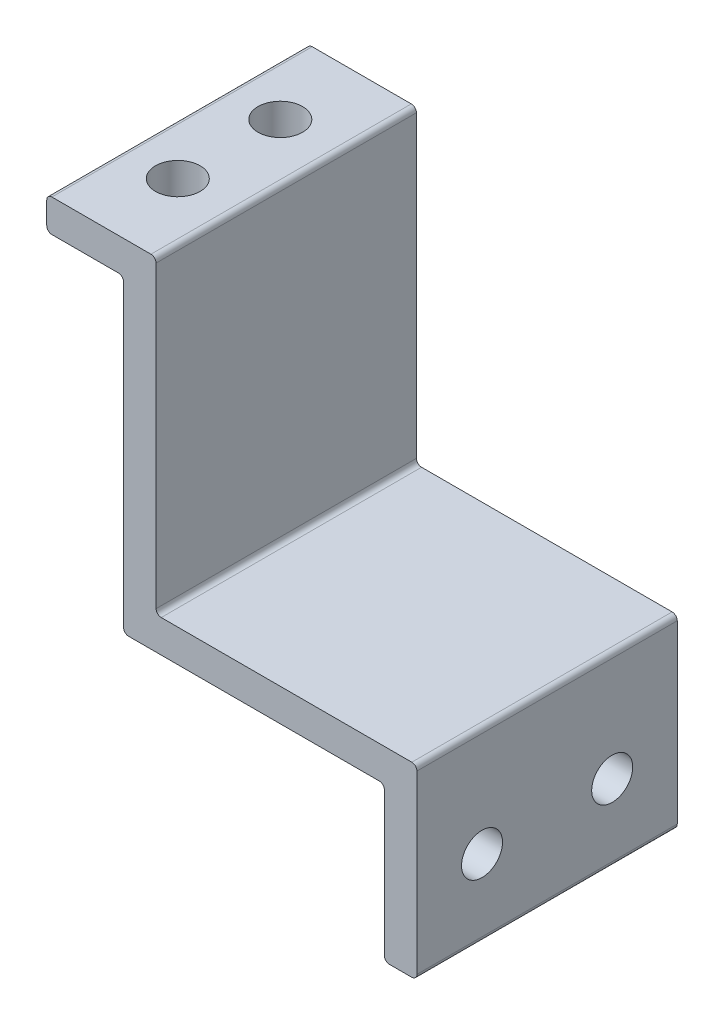
SolidWorks part; units mm, degrees
material "PLA"
ref_plane "Front Plane" through (0, 0, 0) normal (0, 0, 1) x (1, 0, 0)
ref_plane "Top Plane" through (0, 0, 0) normal (0, 1, 0) x (1, 0, 0)
ref_plane "Right Plane" through (0, 0, 0) normal (1, 0, 0) x (0, 0, -1)
sketch "Sketch1" plane through (0, 0, 0) normal (0, 0, 1) x (1, 0, 0)
  line L0 (-96.8188, 43.5162) -> (-96.8188, 40.3412)
  line L1 (-96.8188, 40.3412) -> (-89.3258, 40.3412)
  line L2 (-89.3258, 40.3412) -> (-89.3258, 10.1412)
  line L3 (-89.3258, 10.1412) -> (-63.8758, 10.1412)
  line L4 (-63.8758, 10.1412) -> (-63.8758, -4.8588)
  line L5 (-63.8758, -4.8588) -> (-60.7008, -4.8588)
  line L6 (-60.7008, -4.8588) -> (-60.7008, 13.3162)
  line L7 (-60.7008, 13.3162) -> (-86.1508, 13.3162)
  line L8 (-86.1508, 13.3162) -> (-86.1508, 43.5162)
  line L9 (-86.1508, 43.5162) -> (-96.8188, 43.5162)
  dimension "D1" = 25.45
  dimension "D2" = 3.175
  dimension "D3" = 3.175
  dimension "D4" = 3.175
  dimension "D5" = 30.2
  dimension "D6" = 10.668
  dimension "D7" = 7.493
  dimension "D8" = 3.175
  dimension "D9" = 18.175
extrude "Boss-Extrude1" add sketch "Sketch1" along normal blind 25.4
sketch "Sketch2" plane through (-63.8758, 0, 0) normal (-1, 0, 0) x (0, 0, 1)
  line L0 (12.7, 10.1412) -> (12.7, -4.8588) construction
  line L1 (25.4, 10.1412) -> (0, 10.1412) construction
  line L2 (25.4, -4.8588) -> (0, -4.8588) construction
  line L3 (0, 10.1412) -> (0, -4.8588) construction
  circle A0 centre (6.35, 2.6412) radius 2
  circle A1 centre (19.05, 2.6412) radius 2
  dimension "D1" = 4
  dimension "D3" = 6.35
  dimension "D4" = 7.5
extrude "Cut-Extrude1" cut sketch "Sketch2" against normal through all
fillet "Fillet1" radius 0.5 9 edges at (-86.1508, 43.5162, 12.7) (-86.1508, 13.3162, 12.7) (-60.7008, -4.8588, 12.7) (-60.7008, 13.3162, 12.7) (-63.8758, 10.1412, 12.7) (-63.8758, -4.8588, 12.7) (-89.3258, 10.1412, 12.7) (-96.8188, 43.5162, 12.7) (-96.8188, 40.3412, 12.7)
sketch "Sketch3" plane through (0, 43.5162, 0) normal (0, 1, 0) x (1, 0, 0)
  line L2 (-86.6508, -25.4) -> (-86.6508, 0) construction
  line L3 (-86.6508, 0) -> (-96.3188, 0) construction
  circle A0 centre (-91.7308, -7.7) radius 2.175
  circle A1 centre (-91.7308, -17.7) radius 2.175
  dimension "D1" = 4.35
  dimension "D2" = 4.35
  dimension "D3" = 10
  dimension "D4" = 7.7
  dimension "D5" = 5.08
extrude "Cut-Extrude2" cut sketch "Sketch3" against normal blind 6.604
sketch "Sketch4" plane through (0, 40.3412, 0) normal (0, -1, 0) x (-1, 0, 0)
  circle A0 centre (91.7308, -17.7) radius 4.25
  circle A1 centre (91.7308, -7.7) radius 4.25
  dimension "D1" = 8.5
  dimension "D2" = 8.5
extrude "Cut-Extrude3" cut sketch "Sketch4" along normal blind 5.842
fillet "Fillet2" radius 0.5 13 edges at (-89.3258, 37.4202, 21.2041) (-89.3258, 34.4992, 17.7) (-87.4808, 34.4992, 17.7) (-89.3258, 37.4202, 14.1959) (-89.3258, 37.4202, 11.2041) (-89.3258, 34.4992, 7.7) (-87.4808, 34.4992, 7.7) (-89.3258, 37.4202, 4.1959) (-87.4808, 40.3412, 7.7) (-87.4808, 40.3412, 17.7) (-89.3258, 40.3412, 23.302) (-89.3258, 40.3412, 2.098) (-89.3258, 40.3412, 12.7)
